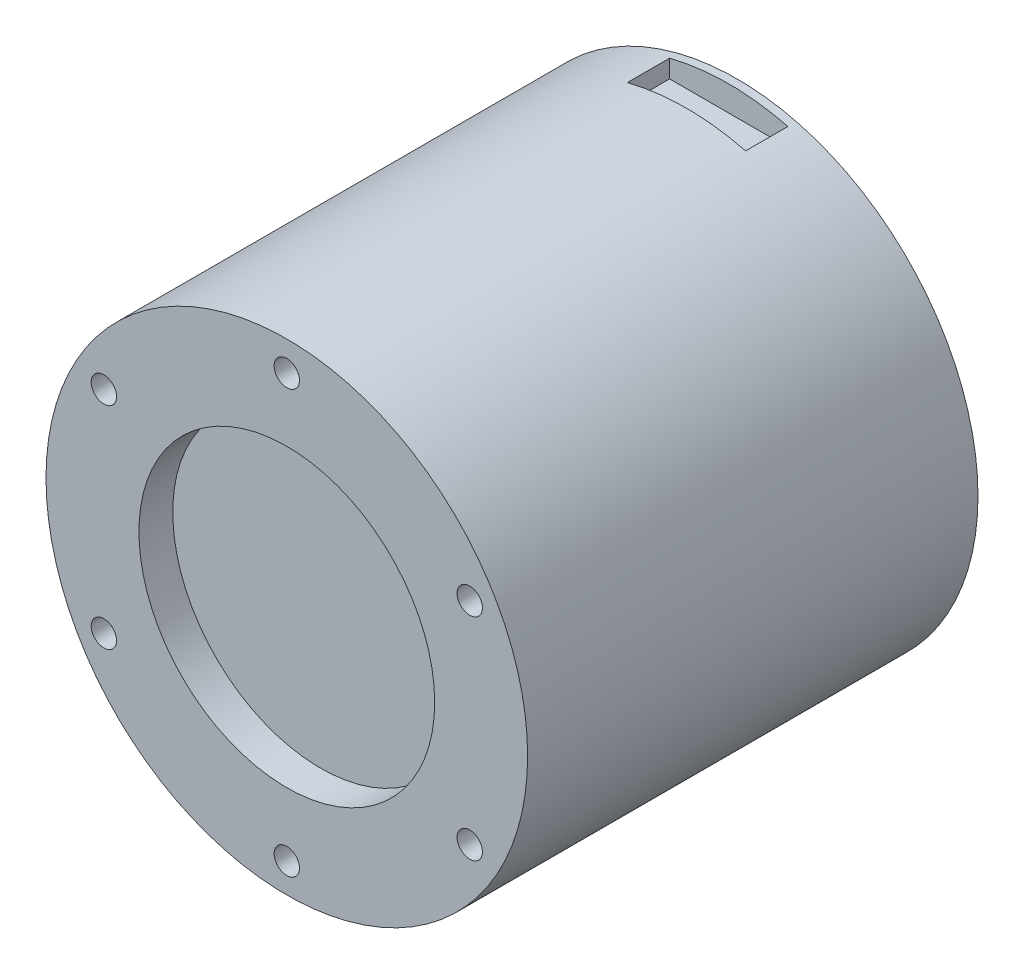
SolidWorks part; units mm, degrees
ref_plane "前视基准面" through (0, 0, 0) normal (0, 0, 1) x (1, 0, 0)
ref_plane "上视基准面" through (0, 0, 0) normal (0, 1, 0) x (1, 0, 0)
ref_plane "右视基准面" through (0, 0, 0) normal (1, 0, 0) x (0, 0, -1)
sketch "草图1" plane through (0, 0, 0) normal (0, 0, 1) x (1, 0, 0)
  circle A0 centre (0, 0) radius 28.5
  dimension "D1" = 57
extrude "凸台-拉伸1" add sketch "草图1" along normal blind 53.3
sketch "草图2" plane through (0, 0, 53.3) normal (0, 0, 1) x (1, 0, 0)
  circle A0 centre (0, 0) radius 17.5
  circle A1 centre (0, 0) radius 25
  circle A2 centre (0, 25) radius 1.5
  circle A3 centre (21.6506, 12.5) radius 1.5
  circle A4 centre (21.6506, -12.5) radius 1.5
  circle A5 centre (0, -25) radius 1.5
  circle A6 centre (-21.6506, -12.5) radius 1.5
  circle A7 centre (-21.6506, 12.5) radius 1.5
  point P18 (0, 0)
  dimension "D1" = 35
  dimension "D2" = 50
  dimension "D3" = 3
  dimension "D4" = 6
extrude "切除-拉伸2" cut sketch "草图2" against normal blind 4 contours A0 region at (0, 0, 53.3)
extrude "切除-拉伸3" cut sketch "草图2<5>" against normal blind 5 contours A2 | A3 | A4 | A5 | A6 | A7
sketch "草图2<5>" plane through (0, 0, 53.3) normal (0, 0, 1) x (1, 0, 0) same geometry as "草图2"
sketch "草图4" plane through (0, 0, 0) normal (0, 0, -1) x (-1, 0, 0)
  line L0 (0, 0) -> (0, 28.5) construction
  line L1 (0, 0) -> (-13.435, 13.435)
  circle A0 centre (0, 0) radius 19
  circle A7 centre (13.435, 13.435) radius 1.5
  circle A8 centre (-13.435, 13.435) radius 1.5
  circle A9 centre (13.435, -13.435) radius 1.5
  circle A10 centre (-13.435, -13.435) radius 1.5
  point P16 (0, 0)
  point P18 (0, 0)
  dimension "D1" = 38
  dimension "D2" = 45
  dimension "D3" = 3
  dimension "D4" = 4
extrude "切除-拉伸4" cut sketch "草图4" against normal blind 4 contours A8 | A7 | A9 | A10
sketch "草图8" plane through (0, 0, 0) normal (0, 1, 0) x (1, 0, 0)
  line L0 (0, 0) -> (0, -41) construction
  line L3 (-7, -1) -> (-7, -6)
  line L5 (-7, -6) -> (7, -6)
  line L6 (7, -6) -> (7, -1)
  line L7 (-7, -1) -> (7, -1)
  line L8 (28.5, 0) -> (-28.5, 0) construction
  point P5 (0, -1)
  dimension "D1" = 14
  dimension "D2" = 5
  dimension "D3" = 1
ref_plane "基准面1" through (0, 28.5, 0) normal (0, 1, 0) x (1, 0, 0)
sketch "草图9" plane through (0, 28.5, 0) normal (0, 1, 0) x (1, 0, 0)
  line L0 (-7, -1) -> (-7, -6)
  line L1 (-7, -6) -> (7, -6)
  line L2 (7, -6) -> (7, -1)
  line L3 (-7, -1) -> (7, -1)
  line L4 (0, 200000) -> (0, -200041) construction
  line L5 (28.5, 0) -> (-28.5, 0) construction
  point P2 (0, -1)
  dimension "D1" = 14
  dimension "D2" = 5
  dimension "D3" = 1
extrude "切除-拉伸6" cut sketch "草图9" against normal blind 3
mirror "镜向1" about plane through (0, 0, 0) normal (0, 1, 0) of "切除-拉伸6"
ref_plane "基准面2" through (-28.5, 0, 0) normal (1, 0, 0) x (0, 0, -1)
sketch "草图10" plane through (-28.5, 0, 0) normal (1, 0, 0) x (0, 0, -1)
  line L0 (-1, 4) -> (-1, -4)
  line L1 (-1, 4) -> (-9, 4)
  line L2 (-9, 4) -> (-9, -4)
  line L3 (-9, -4) -> (-1, -4)
  line L4 (0, -28.5) -> (0, 28.5) construction
  line L6 (-43.3986, 0) -> (5.7011, 0) construction
  point P6 (-1, 0)
  dimension "D1" = 8
  dimension "D2" = 8
  dimension "D3" = 1
extrude "切除-拉伸7" cut sketch "草图10" along normal blind 3
